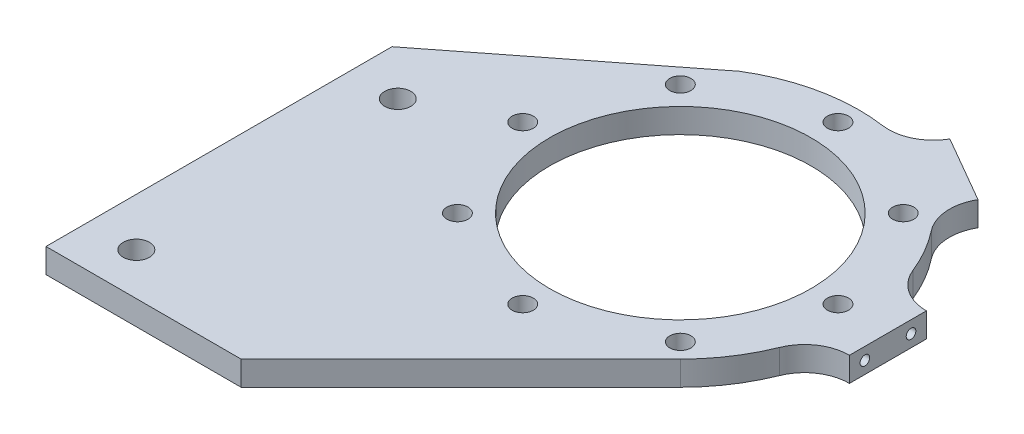
SolidWorks part; units mm, degrees
material "6061 Alloy"
ref_plane "Front Plane" through (0, 0, 0) normal (0, 0, 1) x (1, 0, 0)
ref_plane "Top Plane" through (0, 0, 0) normal (0, 1, 0) x (1, 0, 0)
ref_plane "Right Plane" through (0, 0, 0) normal (1, 0, 0) x (0, 0, -1)
sketch "Sketch2" plane through (0, 0, 0) normal (0, 1, 0) x (1, 0, 0)
  line L0 (50.7609, 129.6827) -> (50.7609, 0) construction
  line L1 (0, 0) -> (50.7609, 0)
  line L2 (0, 0) -> (0, 90)
  line L6 (107.8805, 57.1195) -> (50.7609, 0)
  line L8 (0, 129.6827) -> (0, 90) construction
  line L9 (0, 90) -> (75, 90) construction
  line L10 (0, 90) -> (50.7609, 129.6827)
  arc A1 (50.7609, 129.6827) -> (107.8805, 57.1195) centre (75, 90) cw
  dimension "D1" = 90
  dimension "46.5" = 46.5
  dimension "D2" = 75
  dimension "D5" = 45
base flange "Base-Flange1" sketch "Sketch2" thickness 6.35 reverse thickness direction no parameters "D1"=0.7366
sketch "Sketch8" plane through (0, 0, 0) normal (0, 1, 0) x (1, 0, 0)
  line L1 (0, 90) -> (0, 0) construction
  line L2 (0, 45) -> (79.3207, 45) construction
  line L3 (0, 90) -> (121.5, 90) construction
  line L4 (79.3207, 28.5598) -> (79.3207, 90) construction
  line L5 (50.7609, 0) -> (107.8805, 57.1195) construction
  line L6 (0, 90) -> (0, 0) construction
  circle A1 centre (12.5, 79) radius 3.4
  circle A3 centre (12.5, 11) radius 3.4
  arc A4 (107.8805, 57.1195) -> (50.7609, 129.6827) centre (75, 90) ccw construction
  dimension "D1" = 6.8
  dimension "D3" = 12.5
  dimension "D2" = 11
extrude "Cut-Extrude1" cut sketch "Sketch8" against normal through all normal cut yes
sketch "Sketch9" plane through (0, 0, 0) normal (0, 1, 0) x (1, 0, 0)
  arc A0 (107.8805, 57.1195) -> (50.7609, 129.6827) centre (75, 90) ccw construction
  arc A1 (107.8805, 57.1195) -> (50.7609, 129.6827) centre (75, 90) ccw construction
  circle A2 centre (75, 90) radius 34
  dimension "D1" = 68
extrude "Cut-Extrude2" cut sketch "Sketch9" against normal through all normal cut yes
sketch "Sketch10" plane through (0, 0, 0) normal (0, 1, 0) x (1, 0, 0)
  circle A0 centre (75, 90) radius 41 construction
  circle A1 centre (75, 131) radius 2.75
  circle A2 centre (103.9914, 118.9914) radius 2.75
  circle A3 centre (116, 90) radius 2.75
  circle A4 centre (103.9914, 61.0086) radius 2.75
  circle A5 centre (75, 49) radius 2.75
  circle A6 centre (46.0086, 61.0086) radius 2.75
  circle A7 centre (34, 90) radius 2.75
  circle A8 centre (46.0086, 118.9914) radius 2.75
  point P22 (75, 90)
  dimension "D1" = 82
  dimension "D2" = 5.5
  dimension "D3" = 8
extrude "Cut-Extrude3" cut sketch "Sketch10" against normal through all normal cut yes
sketch "Sketch11" plane through (0, -6.35, 0) normal (0, -1, 0) x (1, 0, 0)
  line L0 (75, -90) -> (129, -90) construction
  line L1 (129, -100) -> (129, -80)
  line L2 (129, -80) -> (120.412, -80) construction
  arc A0 (50.7609, -129.6827) -> (107.8805, -57.1195) centre (75, -90) ccw construction
  arc A1 (50.7609, -129.6827) -> (107.8805, -57.1195) centre (75, -90) ccw construction
  arc A2 (118.1479, -72.6648) -> (129, -80) centre (129, -68.3048) ccw
  arc A3 (118.1479, -107.3352) -> (129, -100) centre (129, -111.6952) cw
  arc A4 (118.1479, -72.6648) -> (118.1479, -107.3352) centre (75, -90) cw
  point P3 (121.5, -90)
  dimension "7,5" = 7.5
  dimension "D2" = 20
extrude "Tabs_1" add sketch "Sketch11" against normal up to surface (6.35 mm away) up to face at (75, 0, -128.25)
hole_wizard "Tabs_2" positions "Sketch18" profile "Sketch20" hole size "M3x0.5" standard "ANSI Metric"
sketch "Sketch18" plane through (129, 0, 0) normal (1, 0, 0) x (0, 0, -1)
  line L1 (80, 0) -> (80, -6.35) construction
  line L2 (100, -6.35) -> (80, -6.35) construction
  line L3 (90, -6.35) -> (90, 0) construction
  line L4 (80, 0) -> (100, 0) construction
  point P0 (84, -3.175)
  point P7 (80, -3.175)
  point P24 (96, -3.175)
  dimension "D1" = 4
sketch "Sketch20" plane through (129, -3.175, -84) normal (0, 1, 0) x (0, 0, -1)
  line L0 (0, 0) -> (0, 5.7511)
  line L1 (0, 5.7511) -> (1.25, 5)
  line L2 (1.25, 5) -> (1.25, 0)
  line L5 (1.25, 0) -> (0, 0)
  line L10 (0, 5.7511) -> (-1.25, 5) construction
  line L11 (0, -6.35) -> (0, 107.95) construction
  dimension "Hole Dia." = 2.5
  dimension "Hole Depth" = 5
  dimension "Drill Angle" = 118
pattern_circular "CirPattern2" count 2 every 60 about axis through (75, 0, -90) along (0, 1, 0) of "Tabs_1", "Tabs_2"
sketch "Bend-Lines1" [suppressed] plane through (0, 0, 0) normal (0, 1, 0) x (1, 0, 0)
sketch "Bounding-Box1" [suppressed] plane through (0, 0, 0) normal (0, 1, 0) x (1, 0, 0)
sheet metal parameters "Sheet-Metal1" thickness 6.35 parameters "D1"=0.7366
flat pattern "Flat-Pattern1" [suppressed]
sketch "Bend-Lines2" plane through (0, 0, 0) normal (0, 1, 0) x (1, 0, 0)
sketch3d "Bounding-Box2" [suppressed]
  line L0 (37.25, -37.25, 0) -> (37.25, 37.25, 0) construction
  line L1 (-22.5, -37.25, 0) -> (-22.5, 37.25, 0) construction
  line L2 (37.25, -37.25, 0) -> (-22.5, -37.25, 0) construction
  line L3 (37.25, 37.25, 0) -> (-22.5, 37.25, 0) construction
sheet metal parameters "Sheet-Metal2" thickness 6.35 parameters "D1"=0.7366
flat pattern "Flat-Pattern1"
sketch "Bend-Lines2" plane through (0, 0, 0) normal (0, 1, 0) x (1, 0, 0)
sketch3d "Bounding-Box2" [suppressed]
  line L0 (-106, -39.1795, 0) -> (-7.0705, 59.75, 0) construction
  line L1 (-46.25, -98.9295, 0) -> (52.6795, 0, 0) construction
  line L2 (-106, -39.1795, 0) -> (-46.25, -98.9295, 0) construction
  line L3 (-7.0705, 59.75, 0) -> (52.6795, 0, 0) construction
sheet metal parameters "Sheet-Metal3" thickness 6.35 parameters "D1"=0.7366
flat pattern "Flat-Pattern1"
sketch "Bend-Lines2" plane through (0, 0, 0) normal (0, 1, 0) x (1, 0, 0)
sketch3d "Bounding-Box2" [suppressed]
  line L0 (-107.7298, -46.3484, 0) -> (0.0689, 64.7304, 0) construction
  line L1 (-42.0452, -110.0934, 0) -> (65.7535, 0.9853, 0) construction
  line L2 (-107.7298, -46.3484, 0) -> (-42.0452, -110.0934, 0) construction
  line L3 (0.0689, 64.7304, 0) -> (65.7535, 0.9853, 0) construction
sheet metal parameters "Sheet-Metal4" thickness 6.35 parameters "D1"=0.7366
flat pattern "Flat-Pattern1"
sketch "Bend-Lines2" plane through (0, 0, 0) normal (0, 1, 0) x (1, 0, 0)
sketch3d "Bounding-Box2" [suppressed]
  line L0 (-120, -45, 0) -> (-4.6195, 70.3805, 0) construction
  line L1 (-49.6195, -115.3805, 0) -> (65.7609, 0, 0) construction
  line L2 (-120, -45, 0) -> (-49.6195, -115.3805, 0) construction
  line L3 (-4.6195, 70.3805, 0) -> (65.7609, 0, 0) construction
sheet metal parameters "Sheet-Metal5" thickness 6.35 parameters "D1"=0.7366
flat pattern "Flat-Pattern1"
sketch "Bend-Lines2" plane through (0, 0, 0) normal (0, 1, 0) x (1, 0, 0)
sketch3d "Bounding-Box2" [suppressed]
  line L0 (-120, -45, 0) -> (-4.6195, 70.3805, 0) construction
  line L1 (-49.6195, -115.3805, 0) -> (65.7609, 0, 0) construction
  line L2 (-120, -45, 0) -> (-49.6195, -115.3805, 0) construction
  line L3 (-4.6195, 70.3805, 0) -> (65.7609, 0, 0) construction
sheet metal parameters "Sheet-Metal7" thickness 6.35 parameters "D1"=0.7366
flat pattern "Flat-Pattern1"
sketch "Bend-Lines2" plane through (0, 0, 0) normal (0, 1, 0) x (1, 0, 0)
sketch3d "Bounding-Box2" [suppressed]
  line L0 (-120, -45, 0) -> (-4.6195, 70.3805, 0) construction
  line L1 (-49.6195, -115.3805, 0) -> (65.7609, 0, 0) construction
  line L2 (-120, -45, 0) -> (-49.6195, -115.3805, 0) construction
  line L3 (-4.6195, 70.3805, 0) -> (65.7609, 0, 0) construction
sheet metal parameters "Sheet-Metal8" thickness 6.35 parameters "D1"=0.7366
flat pattern "Flat-Pattern1"
sketch "Bend-Lines2" plane through (0, 0, 0) normal (0, 1, 0) x (1, 0, 0)
sketch3d "Bounding-Box2" [suppressed]
  line L0 (-120, -45, 0) -> (1.2128, 76.2128, 0) construction
  line L1 (-49.6195, -115.3805, 0) -> (71.5933, 5.8323, 0) construction
  line L2 (-120, -45, 0) -> (-49.6195, -115.3805, 0) construction
  line L3 (1.2128, 76.2128, 0) -> (71.5933, 5.8323, 0) construction
equation "\"L1L\"=500"
equation "\"L1Thick\"=6.35"
equation "\"Harm-Drive-Outer\"=74.5"
equation "\"L1-Spacing\"=115.65"
equation "\"L-Bracket-HoleToWall\"=12.5"
equation "\"Bracket-Hole-D\"=6.8"
equation "\"D1@Sketch8\"=\"Bracket-Hole-D\""
equation "\"L-Bracket-HoleToSide\"=11"
equation "\"D3@Sketch8\"=\"L-Bracket-HoleToWall\""
equation "\"D2@Sketch8\"=\"L-Bracket-HoleToSide\""
